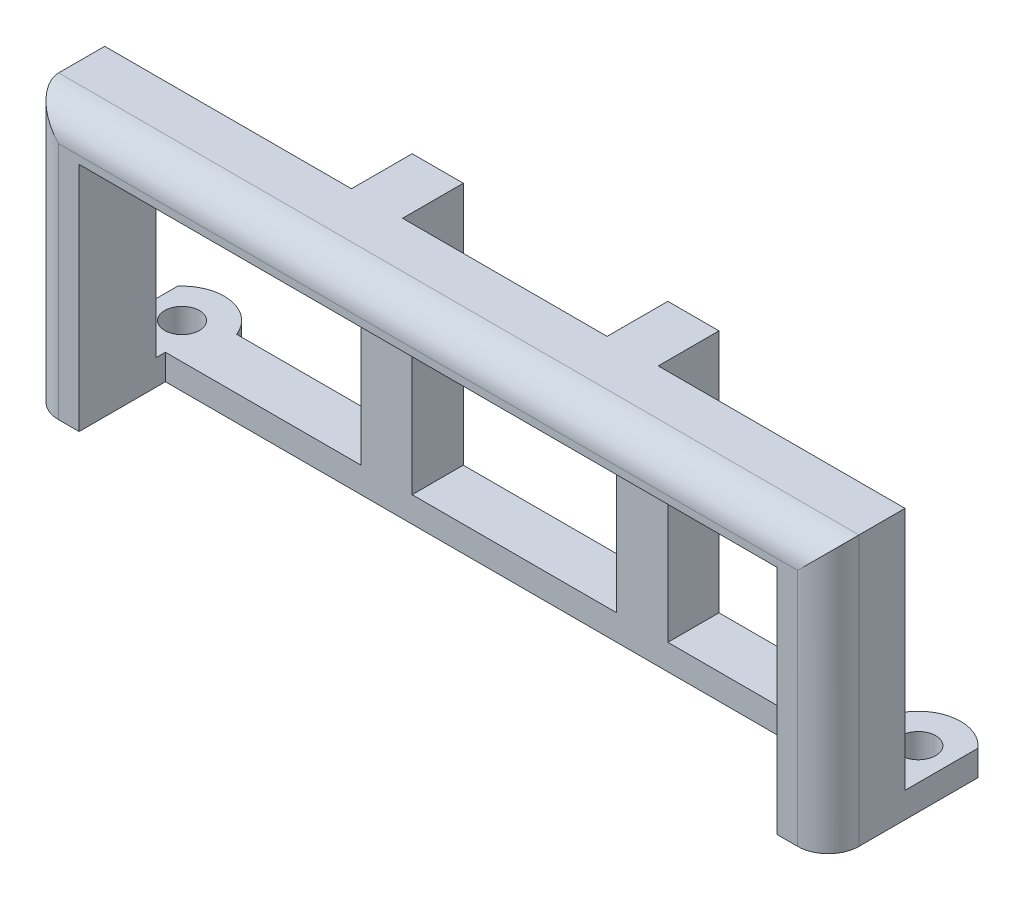
SolidWorks part; units mm, degrees
material "mat_restraint_mat"
ref_plane "Front Plane" through (0, 0, 0) normal (0, 0, 1) x (1, 0, 0)
ref_plane "Top Plane" through (0, 0, 0) normal (0, 1, 0) x (1, 0, 0)
ref_plane "Right Plane" through (0, 0, 0) normal (1, 0, 0) x (0, 0, -1)
sketch "Sketch1" plane through (0, 0, 0) normal (0, 1, 0) x (1, 0, 0)
  line L1 (-49.6887, -4.7625) -> (49.6888, -4.7625)
  line L2 (-49.6887, -4.7625) -> (-49.6887, 4.7625)
  line L3 (-49.6887, 4.7625) -> (49.6888, 4.7625)
  line L4 (49.6888, -4.7625) -> (49.6888, 4.7625)
  line L5 (-49.6887, -4.7625) -> (49.6888, 4.7625) construction
  line L6 (-49.6887, 4.7625) -> (49.6888, -4.7625) construction
  line L7 (-49.6887, 4.7625) -> (-43.3387, 4.7625)
  line L8 (-49.6887, 4.7625) -> (-49.6887, -4.7625)
  line L9 (-49.6887, -4.7625) -> (-43.3387, -4.7625)
  line L10 (-43.3387, 4.7625) -> (-43.3387, -4.7625)
  line L11 (49.6888, 4.7625) -> (43.3388, 4.7625)
  line L12 (49.6888, 4.7625) -> (49.6888, -4.7625)
  line L13 (49.6888, -4.7625) -> (43.3388, -4.7625)
  line L14 (43.3388, 4.7625) -> (43.3388, -4.7625)
  line L19 (-19.05, 4.7625) -> (-12.7, 4.7625)
  line L20 (-19.05, 4.7625) -> (-19.05, 12.3031)
  line L21 (-19.05, 12.3031) -> (-12.7, 12.3031)
  line L22 (-12.7, 4.7625) -> (-12.7, 12.3031)
  line L23 (-19.05, 12.3031) -> (-12.7, 12.3031)
  line L24 (-19.05, 12.3031) -> (-19.05, 5.9531)
  line L25 (-19.05, 5.9531) -> (-12.7, 5.9531)
  line L26 (-12.7, 12.3031) -> (-12.7, 5.9531)
  point P0 (0, 0)
  dimension "D1" = 86.6775
  dimension "D2" = 6.35
  dimension "D3" = 9.525
  dimension "D4" = 6.35
  dimension "D5" = 6.35
  dimension "D6" = 12.7
  dimension "D7" = 7.5406
  dimension "D8" = 6.35
extrude "Boss-Extrude1" add sketch "Sketch1" along normal blind 4.7625 contours L14 L3 L10 L1 | L8 L7 L10 L9 | L12 L11 L14 L13 | L20 L19 L22 L21 region at (0, 0, 0)
extrude "Boss-Extrude2" add sketch "Sketch1<3>" against normal blind 28.7338 contours L10 L3 L2 L1 | L3 L14 L1 L4 | L24 L23 L26 L25 region at (-46.5137, 0, 0) region at (46.5138, 0, 0)
sketch "Sketch1<3>" plane through (0, 0, 0) normal (0, 1, 0) x (1, 0, 0) same geometry as "Sketch1"
mirror "Mirror1" about plane through (0, 0, 0) normal (1, 0, 0) of bodies 102
sketch "Sketch2" plane through (0, -28.7338, 0) normal (0, -1, 0) x (1, 0, 0)
  line L1 (-12.7, -5.9531) -> (0, -5.9531)
  line L2 (-12.7, -5.9531) -> (-12.7, -12.3031)
  line L3 (-12.7, -12.3031) -> (0, -12.3031)
  line L5 (-19.05, -12.3031) -> (-12.7, -12.3031) construction
  line L6 (0, 0) -> (0, -37.3923) construction
  line L11 (-49.6887, 4.7625) -> (-49.6887, -13.8144)
  line L13 (-19.05, -12.3031) -> (-12.7, -12.3031) construction
  line L14 (-15.875, -12.3031) -> (-15.875, -5.9531)
  line L15 (-19.05, -5.9531) -> (-12.7, -5.9531) construction
  line L16 (-49.6887, 4.7625) -> (-43.3387, 4.7625)
  line L17 (-43.3387, 4.7625) -> (-43.3387, -5.9531)
  line L18 (-43.3387, -5.9531) -> (-15.875, -5.9531)
  line L25 (0, -5.9531) -> (0, -12.3031)
  line L30 (-40.8422, -12.3031) -> (-15.875, -12.3031)
  circle A1 centre (-45.72, -10.3981) radius 2.1527
  arc A3 (-49.6887, -13.8144) -> (-40.8422, -12.3031) centre (-45.72, -10.3981) ccw
  dimension "D2" = 4.445
  dimension "D3" = 4.3053
  dimension "D1" = 45.72
extrude "Boss-Extrude3" add sketch "Sketch2" against normal blind 3.175
fillet "Fillet8" [suppressed] radius 6.35
fillet "Fillet7" [suppressed] radius 6.35
mirror "Mirror3" about plane through (0, 0, 0) normal (1, 0, 0) of "Fillet8", "Boss-Extrude3"
fillet "Fillet9" [suppressed] radius 3.81
fillet "Fillet10" [suppressed] radius 6.35
fillet "Fillet11" radius 3.81 3 edges at (49.6888, -11.9856, 4.7625) (-49.6887, -11.9856, 4.7625) (0, 4.7625, 4.7625)
